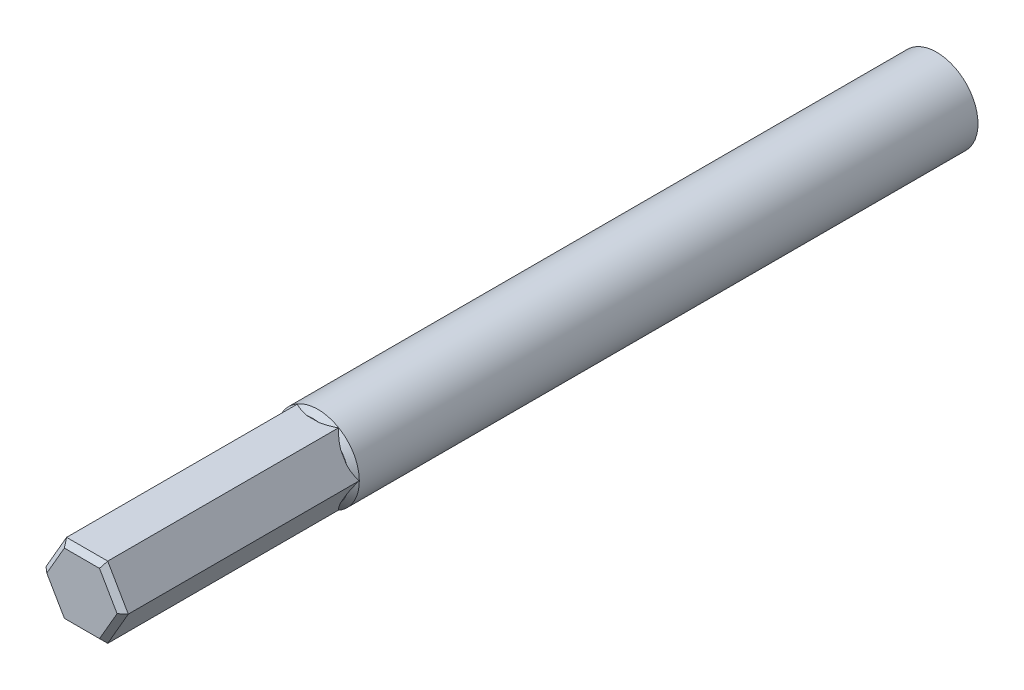
SolidWorks part; units mm, degrees
material "PETG"
ref_plane "Front Plane" through (0, 0, 0) normal (0, 0, 1) x (1, 0, 0)
ref_plane "Top Plane" through (0, 0, 0) normal (0, 1, 0) x (1, 0, 0)
ref_plane "Right Plane" through (0, 0, 0) normal (1, 0, 0) x (0, 0, -1)
sketch "Sketch1" plane through (0, 0, 0) normal (0, 0, 1) x (1, 0, 0)
  circle A0 centre (0, 0) radius 3.975
  dimension "Shaft Dia" = 7.95
extrude "Boss-Extrude1" add sketch "Sketch1" along normal blind 60
sketch "Sketch2" plane through (0, 0, 60) normal (0, 0, 1) x (1, 0, 0)
  line L1 (4, 0) -> (2, 3.4641) construction
  line L2 (2, 3.4641) -> (-2, 3.4641) construction
  line L3 (-2, 3.4641) -> (-4, 0) construction
  line L4 (-4, 0) -> (-2, -3.4641) construction
  line L5 (-2, -3.4641) -> (2, -3.4641) construction
  line L6 (2, -3.4641) -> (4, 0) construction
  line L7 (3.9567, 0) -> (1.9783, 3.4266)
  line L8 (1.9783, 3.4266) -> (-1.9783, 3.4266)
  line L9 (-1.9783, 3.4266) -> (-3.9567, 0)
  line L10 (-3.9567, 0) -> (-1.9783, -3.4266)
  line L11 (-1.9783, -3.4266) -> (1.9783, -3.4266)
  line L12 (1.9783, -3.4266) -> (3.9567, 0)
  circle A0 centre (0, 0) radius 3.4641 construction
  circle A1 centre (0, 0) radius 3.4266 construction
  dimension "Hex Circumscribed Nominal Dia" = 8
  dimension "Hex Flat To Flat Offset" = 0.0375
extrude "Boss-Extrude2" add sketch "Sketch2" along normal blind 22.2
chamfer "Chamfer1" distance 0.5 angle 45 7 edges at (0, -3.4266, 82.2) (-2.9675, -1.7133, 82.2) (-2.9675, 1.7133, 82.2) (0, 3.4266, 82.2) (2.9675, 1.7133, 82.2) (2.9675, -1.7133, 82.2) (3.975, 0, 60)
equation "\"tol_dia_id_intfc\" = 0.0500mm ' For hole diameters - Interference fit"
equation "\"tol_dia_id_slip\"  = 0.0750mm ' For hole diameters - Slip fit"
equation "\"tol_dia_id_clear\" = 0.1000mm ' For hole diameters - Clearance fit"
equation "\"tol_dia_od_intfc\" = 0.0500mm ' For shaft diameters - Interference fit"
equation "\"tol_dia_od_slip\"  = 0.0750mm ' For shaft diameters - Slip fit"
equation "\"tol_dia_od_clear\" = 0.1000mm ' For shaft diameters - Clearance fit"
equation "\"tol_general_intfc\"= 0.0250mm ' For general parts (Horiz) - Interference fit"
equation "\"tol_general_slip\" = 0.0375mm ' For general parts (Horiz) - Slip fit"
equation "\"tol_general_clear\"= 0.0500mm ' For general parts (Horiz) - Clearance fit"
equation "\"tol_layer_intfc\"  = 0.0250mm ' For all parts (Vert) - Interference fit"
equation "\"tol_layer_slip\"   = 0.0375mm ' For all parts (Vert) - Slip fit"
equation "\"tol_layer_clear\"  = 0.0500mm ' For all parts (Vert) - Clearance fit"
equation "\"tol_corner_rad\"   = 0.100mm ' For corners that fit into other parts"
equation "\"Shaft Dia@Sketch1\" = \"nominal_dia\" - \"tol_dia_od_intfc\""
equation "\"nominal_dia\"= 8.00mm"
equation "\"Hex Circumscribed Nominal Dia@Sketch2\" = \"nominal_dia\""
equation "\"Hex Flat To Flat Offset@Sketch2\"=\"tol_general_slip\""
equation "\"D1@Fillet1\"=\"tol_corner_rad\""
